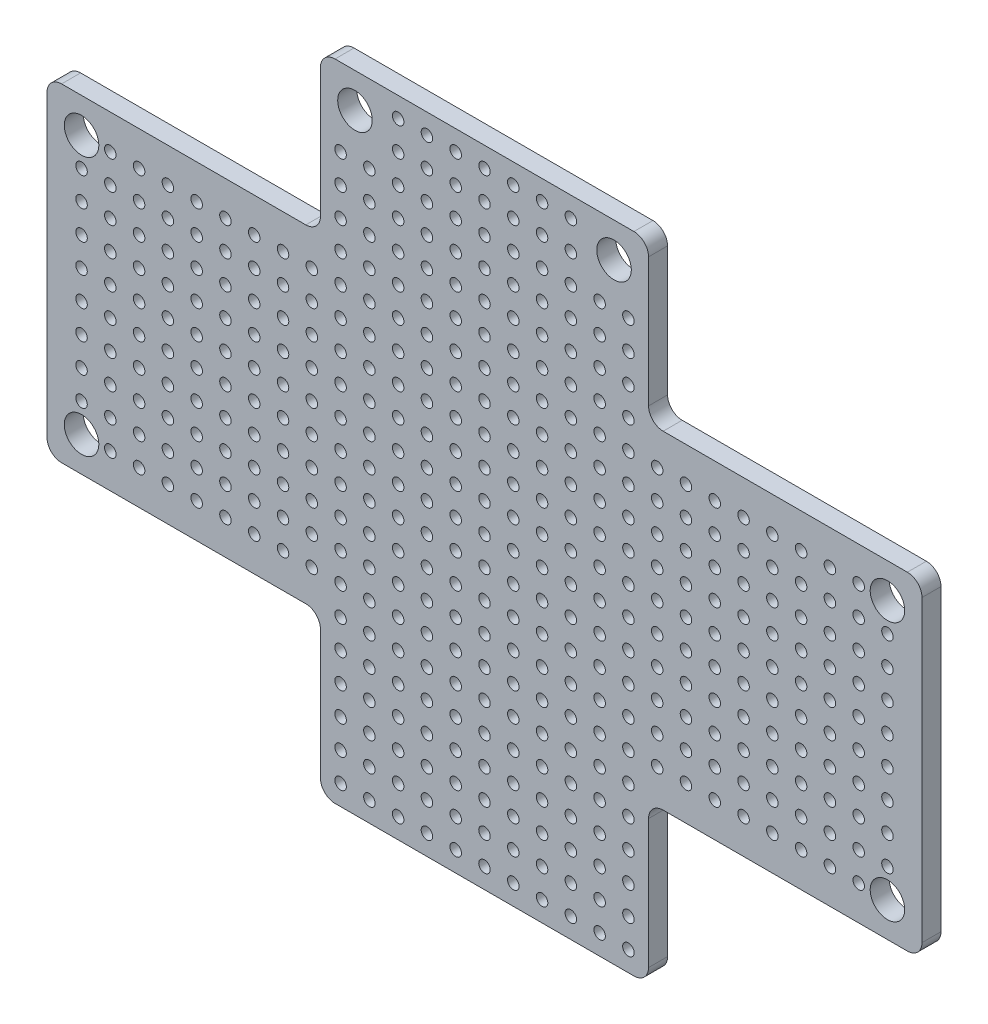
SolidWorks part; units mm, degrees
ref_plane "Front Plane" through (0, 0, 0) normal (0, 0, 1) x (1, 0, 0)
ref_plane "Top Plane" through (0, 0, 0) normal (0, 1, 0) x (1, 0, 0)
ref_plane "Right Plane" through (0, 0, 0) normal (1, 0, 0) x (0, 0, -1)
sketch "Sketch1" plane through (0, 0, 0) normal (0, 0, 1) x (1, 0, 0)
  line L0 (0, 14.25) -> (76, 14.25) construction
  line L1 (0, 0) -> (23.75, 0)
  line L2 (0, 0) -> (0, 28.5)
  line L3 (0, 28.5) -> (23.75, 28.5)
  line L4 (76, 0) -> (76, 28.5)
  line L5 (38, -42.734) -> (38, 127.234) construction
  line L6 (0, 25.5) -> (76, 25.5) construction
  line L7 (76, 3) -> (0, 3) construction
  line L8 (73, 0) -> (73, 28.5) construction
  line L9 (3, 0) -> (3, 28.5) construction
  line L12 (23.75, 28.5) -> (23.75, 42.25)
  line L13 (23.75, 42.25) -> (52.25, 42.25)
  line L14 (52.25, 42.25) -> (52.25, 28.5)
  line L15 (52.25, -13.75) -> (52.25, 0)
  line L16 (23.75, -13.75) -> (52.25, -13.75)
  line L17 (23.75, 0) -> (23.75, -13.75)
  line L18 (52.25, 28.5) -> (76, 28.5)
  line L19 (52.25, 0) -> (76, 0)
  line L20 (25.5, 25.5) -> (25.5, 28) construction
  circle A0 centre (3, 25.5) radius 1.5
  circle A1 centre (73, 25.5) radius 1.5
  circle A2 centre (3, 3) radius 1.5
  circle A3 centre (73, 3) radius 1.5
  circle A4 centre (26.75, 39.25) radius 1.5
  circle A5 centre (5.5, 3) radius 0.5
  circle A6 centre (8, 3) radius 0.5
  circle A7 centre (10.5, 3) radius 0.5
  circle A8 centre (13, 3) radius 0.5
  circle A9 centre (15.5, 3) radius 0.5
  circle A10 centre (18, 3) radius 0.5
  circle A11 centre (20.5, 3) radius 0.5
  circle A12 centre (23, 3) radius 0.5
  circle A13 centre (25.5, 3) radius 0.5
  circle A14 centre (28, 3) radius 0.5
  circle A15 centre (30.5, 3) radius 0.5
  circle A16 centre (33, 3) radius 0.5
  circle A17 centre (35.5, 3) radius 0.5
  circle A18 centre (38, 3) radius 0.5
  circle A19 centre (40.5, 3) radius 0.5
  circle A20 centre (43, 3) radius 0.5
  circle A21 centre (45.5, 3) radius 0.5
  circle A22 centre (48, 3) radius 0.5
  circle A23 centre (50.5, 3) radius 0.5
  circle A24 centre (53, 3) radius 0.5
  circle A25 centre (55.5, 3) radius 0.5
  circle A26 centre (58, 3) radius 0.5
  circle A27 centre (60.5, 3) radius 0.5
  circle A28 centre (63, 3) radius 0.5
  circle A29 centre (65.5, 3) radius 0.5
  circle A30 centre (68, 3) radius 0.5
  circle A31 centre (70.5, 3) radius 0.5
  circle A32 centre (49.25, 39.25) radius 1.5
  circle A33 centre (5.5, 5.5) radius 0.5
  circle A34 centre (8, 5.5) radius 0.5
  circle A35 centre (10.5, 5.5) radius 0.5
  circle A36 centre (13, 5.5) radius 0.5
  circle A37 centre (15.5, 5.5) radius 0.5
  circle A38 centre (18, 5.5) radius 0.5
  circle A39 centre (20.5, 5.5) radius 0.5
  circle A40 centre (23, 5.5) radius 0.5
  circle A41 centre (25.5, 5.5) radius 0.5
  circle A42 centre (28, 5.5) radius 0.5
  circle A43 centre (30.5, 5.5) radius 0.5
  circle A44 centre (33, 5.5) radius 0.5
  circle A45 centre (35.5, 5.5) radius 0.5
  circle A46 centre (38, 5.5) radius 0.5
  circle A47 centre (40.5, 5.5) radius 0.5
  circle A48 centre (43, 5.5) radius 0.5
  circle A49 centre (45.5, 5.5) radius 0.5
  circle A50 centre (48, 5.5) radius 0.5
  circle A51 centre (50.5, 5.5) radius 0.5
  circle A52 centre (53, 5.5) radius 0.5
  circle A53 centre (55.5, 5.5) radius 0.5
  circle A54 centre (58, 5.5) radius 0.5
  circle A55 centre (60.5, 5.5) radius 0.5
  circle A56 centre (63, 5.5) radius 0.5
  circle A57 centre (65.5, 5.5) radius 0.5
  circle A58 centre (68, 5.5) radius 0.5
  circle A59 centre (70.5, 5.5) radius 0.5
  circle A60 centre (73, 5.5) radius 0.5
  circle A61 centre (5.5, 8) radius 0.5
  circle A62 centre (8, 8) radius 0.5
  circle A63 centre (10.5, 8) radius 0.5
  circle A64 centre (13, 8) radius 0.5
  circle A65 centre (15.5, 8) radius 0.5
  circle A66 centre (18, 8) radius 0.5
  circle A67 centre (20.5, 8) radius 0.5
  circle A68 centre (23, 8) radius 0.5
  circle A69 centre (25.5, 8) radius 0.5
  circle A70 centre (28, 8) radius 0.5
  circle A71 centre (30.5, 8) radius 0.5
  circle A72 centre (33, 8) radius 0.5
  circle A73 centre (35.5, 8) radius 0.5
  circle A74 centre (38, 8) radius 0.5
  circle A75 centre (40.5, 8) radius 0.5
  circle A76 centre (43, 8) radius 0.5
  circle A77 centre (45.5, 8) radius 0.5
  circle A78 centre (48, 8) radius 0.5
  circle A79 centre (50.5, 8) radius 0.5
  circle A80 centre (53, 8) radius 0.5
  circle A81 centre (55.5, 8) radius 0.5
  circle A82 centre (58, 8) radius 0.5
  circle A83 centre (60.5, 8) radius 0.5
  circle A84 centre (63, 8) radius 0.5
  circle A85 centre (65.5, 8) radius 0.5
  circle A86 centre (68, 8) radius 0.5
  circle A87 centre (70.5, 8) radius 0.5
  circle A88 centre (73, 8) radius 0.5
  circle A89 centre (5.5, 10.5) radius 0.5
  circle A90 centre (8, 10.5) radius 0.5
  circle A91 centre (10.5, 10.5) radius 0.5
  circle A92 centre (13, 10.5) radius 0.5
  circle A93 centre (15.5, 10.5) radius 0.5
  circle A94 centre (18, 10.5) radius 0.5
  circle A95 centre (20.5, 10.5) radius 0.5
  circle A96 centre (23, 10.5) radius 0.5
  circle A97 centre (25.5, 10.5) radius 0.5
  circle A98 centre (28, 10.5) radius 0.5
  circle A99 centre (30.5, 10.5) radius 0.5
  circle A100 centre (33, 10.5) radius 0.5
  circle A101 centre (35.5, 10.5) radius 0.5
  circle A102 centre (38, 10.5) radius 0.5
  circle A103 centre (40.5, 10.5) radius 0.5
  circle A104 centre (43, 10.5) radius 0.5
  circle A105 centre (45.5, 10.5) radius 0.5
  circle A106 centre (48, 10.5) radius 0.5
  circle A107 centre (50.5, 10.5) radius 0.5
  circle A108 centre (53, 10.5) radius 0.5
  circle A109 centre (55.5, 10.5) radius 0.5
  circle A110 centre (58, 10.5) radius 0.5
  circle A111 centre (60.5, 10.5) radius 0.5
  circle A112 centre (63, 10.5) radius 0.5
  circle A113 centre (65.5, 10.5) radius 0.5
  circle A114 centre (68, 10.5) radius 0.5
  circle A115 centre (70.5, 10.5) radius 0.5
  circle A116 centre (73, 10.5) radius 0.5
  circle A117 centre (5.5, 13) radius 0.5
  circle A118 centre (8, 13) radius 0.5
  circle A119 centre (10.5, 13) radius 0.5
  circle A120 centre (13, 13) radius 0.5
  circle A121 centre (15.5, 13) radius 0.5
  circle A122 centre (18, 13) radius 0.5
  circle A123 centre (20.5, 13) radius 0.5
  circle A124 centre (23, 13) radius 0.5
  circle A125 centre (25.5, 13) radius 0.5
  circle A126 centre (28, 13) radius 0.5
  circle A127 centre (30.5, 13) radius 0.5
  circle A128 centre (33, 13) radius 0.5
  circle A129 centre (35.5, 13) radius 0.5
  circle A130 centre (38, 13) radius 0.5
  circle A131 centre (40.5, 13) radius 0.5
  circle A132 centre (43, 13) radius 0.5
  circle A133 centre (45.5, 13) radius 0.5
  circle A134 centre (48, 13) radius 0.5
  circle A135 centre (50.5, 13) radius 0.5
  circle A136 centre (53, 13) radius 0.5
  circle A137 centre (55.5, 13) radius 0.5
  circle A138 centre (58, 13) radius 0.5
  circle A139 centre (60.5, 13) radius 0.5
  circle A140 centre (63, 13) radius 0.5
  circle A141 centre (65.5, 13) radius 0.5
  circle A142 centre (68, 13) radius 0.5
  circle A143 centre (70.5, 13) radius 0.5
  circle A144 centre (73, 13) radius 0.5
  circle A145 centre (5.5, 15.5) radius 0.5
  circle A146 centre (8, 15.5) radius 0.5
  circle A147 centre (10.5, 15.5) radius 0.5
  circle A148 centre (13, 15.5) radius 0.5
  circle A149 centre (15.5, 15.5) radius 0.5
  circle A150 centre (18, 15.5) radius 0.5
  circle A151 centre (20.5, 15.5) radius 0.5
  circle A152 centre (23, 15.5) radius 0.5
  circle A153 centre (25.5, 15.5) radius 0.5
  circle A154 centre (28, 15.5) radius 0.5
  circle A155 centre (30.5, 15.5) radius 0.5
  circle A156 centre (33, 15.5) radius 0.5
  circle A157 centre (35.5, 15.5) radius 0.5
  circle A158 centre (38, 15.5) radius 0.5
  circle A159 centre (40.5, 15.5) radius 0.5
  circle A160 centre (43, 15.5) radius 0.5
  circle A161 centre (45.5, 15.5) radius 0.5
  circle A162 centre (48, 15.5) radius 0.5
  circle A163 centre (50.5, 15.5) radius 0.5
  circle A164 centre (53, 15.5) radius 0.5
  circle A165 centre (55.5, 15.5) radius 0.5
  circle A166 centre (58, 15.5) radius 0.5
  circle A167 centre (60.5, 15.5) radius 0.5
  circle A168 centre (63, 15.5) radius 0.5
  circle A169 centre (65.5, 15.5) radius 0.5
  circle A170 centre (68, 15.5) radius 0.5
  circle A171 centre (70.5, 15.5) radius 0.5
  circle A172 centre (73, 15.5) radius 0.5
  circle A173 centre (5.5, 18) radius 0.5
  circle A174 centre (8, 18) radius 0.5
  circle A175 centre (10.5, 18) radius 0.5
  circle A176 centre (13, 18) radius 0.5
  circle A177 centre (15.5, 18) radius 0.5
  circle A178 centre (18, 18) radius 0.5
  circle A179 centre (20.5, 18) radius 0.5
  circle A180 centre (23, 18) radius 0.5
  circle A181 centre (25.5, 18) radius 0.5
  circle A182 centre (28, 18) radius 0.5
  circle A183 centre (30.5, 18) radius 0.5
  circle A184 centre (33, 18) radius 0.5
  circle A185 centre (35.5, 18) radius 0.5
  circle A186 centre (38, 18) radius 0.5
  circle A187 centre (40.5, 18) radius 0.5
  circle A188 centre (43, 18) radius 0.5
  circle A189 centre (45.5, 18) radius 0.5
  circle A190 centre (48, 18) radius 0.5
  circle A191 centre (50.5, 18) radius 0.5
  circle A192 centre (53, 18) radius 0.5
  circle A193 centre (55.5, 18) radius 0.5
  circle A194 centre (58, 18) radius 0.5
  circle A195 centre (60.5, 18) radius 0.5
  circle A196 centre (63, 18) radius 0.5
  circle A197 centre (65.5, 18) radius 0.5
  circle A198 centre (68, 18) radius 0.5
  circle A199 centre (70.5, 18) radius 0.5
  circle A200 centre (73, 18) radius 0.5
  circle A201 centre (5.5, 20.5) radius 0.5
  circle A202 centre (8, 20.5) radius 0.5
  circle A203 centre (10.5, 20.5) radius 0.5
  circle A204 centre (13, 20.5) radius 0.5
  circle A205 centre (15.5, 20.5) radius 0.5
  circle A206 centre (18, 20.5) radius 0.5
  circle A207 centre (20.5, 20.5) radius 0.5
  circle A208 centre (23, 20.5) radius 0.5
  circle A209 centre (25.5, 20.5) radius 0.5
  circle A210 centre (28, 20.5) radius 0.5
  circle A211 centre (30.5, 20.5) radius 0.5
  circle A212 centre (33, 20.5) radius 0.5
  circle A213 centre (35.5, 20.5) radius 0.5
  circle A214 centre (38, 20.5) radius 0.5
  circle A215 centre (40.5, 20.5) radius 0.5
  circle A216 centre (43, 20.5) radius 0.5
  circle A217 centre (45.5, 20.5) radius 0.5
  circle A218 centre (48, 20.5) radius 0.5
  circle A219 centre (50.5, 20.5) radius 0.5
  circle A220 centre (53, 20.5) radius 0.5
  circle A221 centre (55.5, 20.5) radius 0.5
  circle A222 centre (58, 20.5) radius 0.5
  circle A223 centre (60.5, 20.5) radius 0.5
  circle A224 centre (63, 20.5) radius 0.5
  circle A225 centre (65.5, 20.5) radius 0.5
  circle A226 centre (68, 20.5) radius 0.5
  circle A227 centre (70.5, 20.5) radius 0.5
  circle A228 centre (73, 20.5) radius 0.5
  circle A229 centre (5.5, 23) radius 0.5
  circle A230 centre (8, 23) radius 0.5
  circle A231 centre (10.5, 23) radius 0.5
  circle A232 centre (13, 23) radius 0.5
  circle A233 centre (15.5, 23) radius 0.5
  circle A234 centre (18, 23) radius 0.5
  circle A235 centre (20.5, 23) radius 0.5
  circle A236 centre (23, 23) radius 0.5
  circle A237 centre (25.5, 23) radius 0.5
  circle A238 centre (28, 23) radius 0.5
  circle A239 centre (30.5, 23) radius 0.5
  circle A240 centre (33, 23) radius 0.5
  circle A241 centre (35.5, 23) radius 0.5
  circle A242 centre (38, 23) radius 0.5
  circle A243 centre (40.5, 23) radius 0.5
  circle A244 centre (43, 23) radius 0.5
  circle A245 centre (45.5, 23) radius 0.5
  circle A246 centre (48, 23) radius 0.5
  circle A247 centre (50.5, 23) radius 0.5
  circle A248 centre (53, 23) radius 0.5
  circle A249 centre (55.5, 23) radius 0.5
  circle A250 centre (58, 23) radius 0.5
  circle A251 centre (60.5, 23) radius 0.5
  circle A252 centre (63, 23) radius 0.5
  circle A253 centre (65.5, 23) radius 0.5
  circle A254 centre (68, 23) radius 0.5
  circle A255 centre (70.5, 23) radius 0.5
  circle A256 centre (73, 23) radius 0.5
  circle A257 centre (5.5, 25.5) radius 0.5
  circle A258 centre (8, 25.5) radius 0.5
  circle A259 centre (10.5, 25.5) radius 0.5
  circle A260 centre (13, 25.5) radius 0.5
  circle A261 centre (15.5, 25.5) radius 0.5
  circle A262 centre (18, 25.5) radius 0.5
  circle A263 centre (20.5, 25.5) radius 0.5
  circle A264 centre (23, 25.5) radius 0.5
  circle A265 centre (25.5, 25.5) radius 0.5
  circle A266 centre (28, 25.5) radius 0.5
  circle A267 centre (30.5, 25.5) radius 0.5
  circle A268 centre (33, 25.5) radius 0.5
  circle A269 centre (35.5, 25.5) radius 0.5
  circle A270 centre (38, 25.5) radius 0.5
  circle A271 centre (40.5, 25.5) radius 0.5
  circle A272 centre (43, 25.5) radius 0.5
  circle A273 centre (45.5, 25.5) radius 0.5
  circle A274 centre (48, 25.5) radius 0.5
  circle A275 centre (50.5, 25.5) radius 0.5
  circle A276 centre (53, 25.5) radius 0.5
  circle A277 centre (55.5, 25.5) radius 0.5
  circle A278 centre (58, 25.5) radius 0.5
  circle A279 centre (60.5, 25.5) radius 0.5
  circle A280 centre (63, 25.5) radius 0.5
  circle A281 centre (65.5, 25.5) radius 0.5
  circle A282 centre (68, 25.5) radius 0.5
  circle A283 centre (70.5, 25.5) radius 0.5
  circle A285 centre (3, 5.5) radius 0.5
  circle A286 centre (3, 8) radius 0.5
  circle A287 centre (3, 10.5) radius 0.5
  circle A288 centre (3, 13) radius 0.5
  circle A289 centre (3, 15.5) radius 0.5
  circle A290 centre (3, 18) radius 0.5
  circle A291 centre (3, 20.5) radius 0.5
  circle A292 centre (3, 23) radius 0.5
  circle A294 centre (25.5, 28) radius 0.5
  circle A295 centre (28, 28) radius 0.5
  circle A296 centre (30.5, 28) radius 0.5
  circle A297 centre (33, 28) radius 0.5
  circle A298 centre (35.5, 28) radius 0.5
  circle A299 centre (38, 28) radius 0.5
  circle A300 centre (40.5, 28) radius 0.5
  circle A301 centre (43, 28) radius 0.5
  circle A302 centre (45.5, 28) radius 0.5
  circle A303 centre (48, 28) radius 0.5
  circle A304 centre (50.5, 28) radius 0.5
  circle A305 centre (25.5, 30.5) radius 0.5
  circle A306 centre (28, 30.5) radius 0.5
  circle A307 centre (30.5, 30.5) radius 0.5
  circle A308 centre (33, 30.5) radius 0.5
  circle A309 centre (35.5, 30.5) radius 0.5
  circle A310 centre (38, 30.5) radius 0.5
  circle A311 centre (40.5, 30.5) radius 0.5
  circle A312 centre (43, 30.5) radius 0.5
  circle A313 centre (45.5, 30.5) radius 0.5
  circle A314 centre (48, 30.5) radius 0.5
  circle A315 centre (50.5, 30.5) radius 0.5
  circle A316 centre (25.5, 33) radius 0.5
  circle A317 centre (28, 33) radius 0.5
  circle A318 centre (30.5, 33) radius 0.5
  circle A319 centre (33, 33) radius 0.5
  circle A320 centre (35.5, 33) radius 0.5
  circle A321 centre (38, 33) radius 0.5
  circle A322 centre (40.5, 33) radius 0.5
  circle A323 centre (43, 33) radius 0.5
  circle A324 centre (45.5, 33) radius 0.5
  circle A325 centre (48, 33) radius 0.5
  circle A326 centre (50.5, 33) radius 0.5
  circle A327 centre (25.5, 35.5) radius 0.5
  circle A328 centre (28, 35.5) radius 0.5
  circle A329 centre (30.5, 35.5) radius 0.5
  circle A330 centre (33, 35.5) radius 0.5
  circle A331 centre (35.5, 35.5) radius 0.5
  circle A332 centre (38, 35.5) radius 0.5
  circle A333 centre (40.5, 35.5) radius 0.5
  circle A334 centre (43, 35.5) radius 0.5
  circle A335 centre (45.5, 35.5) radius 0.5
  circle A336 centre (48, 35.5) radius 0.5
  circle A337 centre (50.5, 35.5) radius 0.5
  circle A340 centre (30.5, 38) radius 0.5
  circle A341 centre (33, 38) radius 0.5
  circle A342 centre (35.5, 38) radius 0.5
  circle A343 centre (38, 38) radius 0.5
  circle A344 centre (40.5, 38) radius 0.5
  circle A345 centre (43, 38) radius 0.5
  circle A346 centre (45.5, 38) radius 0.5
  circle A351 centre (30.5, 40.5) radius 0.5
  circle A352 centre (33, 40.5) radius 0.5
  circle A353 centre (35.5, 40.5) radius 0.5
  circle A354 centre (38, 40.5) radius 0.5
  circle A355 centre (40.5, 40.5) radius 0.5
  circle A356 centre (43, 40.5) radius 0.5
  circle A357 centre (45.5, 40.5) radius 0.5
  circle A384 centre (25.5, -12) radius 0.5
  circle A385 centre (25.5, -9.5) radius 0.5
  circle A386 centre (25.5, -7) radius 0.5
  circle A387 centre (25.5, -4.5) radius 0.5
  circle A388 centre (25.5, -2) radius 0.5
  circle A389 centre (25.5, 0.5) radius 0.5
  circle A410 centre (50.5, -12) radius 0.5
  circle A411 centre (48, -12) radius 0.5
  circle A412 centre (45.5, -12) radius 0.5
  circle A413 centre (43, -12) radius 0.5
  circle A414 centre (40.5, -12) radius 0.5
  circle A415 centre (38, -12) radius 0.5
  circle A416 centre (35.5, -12) radius 0.5
  circle A417 centre (33, -12) radius 0.5
  circle A418 centre (30.5, -12) radius 0.5
  circle A419 centre (28, -12) radius 0.5
  circle A420 centre (50.5, -9.5) radius 0.5
  circle A421 centre (48, -9.5) radius 0.5
  circle A422 centre (45.5, -9.5) radius 0.5
  circle A423 centre (43, -9.5) radius 0.5
  circle A424 centre (40.5, -9.5) radius 0.5
  circle A425 centre (38, -9.5) radius 0.5
  circle A426 centre (35.5, -9.5) radius 0.5
  circle A427 centre (33, -9.5) radius 0.5
  circle A428 centre (30.5, -9.5) radius 0.5
  circle A429 centre (28, -9.5) radius 0.5
  circle A430 centre (50.5, -7) radius 0.5
  circle A431 centre (48, -7) radius 0.5
  circle A432 centre (45.5, -7) radius 0.5
  circle A433 centre (43, -7) radius 0.5
  circle A434 centre (40.5, -7) radius 0.5
  circle A435 centre (38, -7) radius 0.5
  circle A436 centre (35.5, -7) radius 0.5
  circle A437 centre (33, -7) radius 0.5
  circle A438 centre (30.5, -7) radius 0.5
  circle A439 centre (28, -7) radius 0.5
  circle A440 centre (50.5, -4.5) radius 0.5
  circle A441 centre (48, -4.5) radius 0.5
  circle A442 centre (45.5, -4.5) radius 0.5
  circle A443 centre (43, -4.5) radius 0.5
  circle A444 centre (40.5, -4.5) radius 0.5
  circle A445 centre (38, -4.5) radius 0.5
  circle A446 centre (35.5, -4.5) radius 0.5
  circle A447 centre (33, -4.5) radius 0.5
  circle A448 centre (30.5, -4.5) radius 0.5
  circle A449 centre (28, -4.5) radius 0.5
  circle A450 centre (50.5, -2) radius 0.5
  circle A451 centre (48, -2) radius 0.5
  circle A452 centre (45.5, -2) radius 0.5
  circle A453 centre (43, -2) radius 0.5
  circle A454 centre (40.5, -2) radius 0.5
  circle A455 centre (38, -2) radius 0.5
  circle A456 centre (35.5, -2) radius 0.5
  circle A457 centre (33, -2) radius 0.5
  circle A458 centre (30.5, -2) radius 0.5
  circle A459 centre (28, -2) radius 0.5
  circle A460 centre (50.5, 0.5) radius 0.5
  circle A461 centre (48, 0.5) radius 0.5
  circle A462 centre (45.5, 0.5) radius 0.5
  circle A463 centre (43, 0.5) radius 0.5
  circle A464 centre (40.5, 0.5) radius 0.5
  circle A465 centre (38, 0.5) radius 0.5
  circle A466 centre (35.5, 0.5) radius 0.5
  circle A467 centre (33, 0.5) radius 0.5
  circle A468 centre (30.5, 0.5) radius 0.5
  circle A469 centre (28, 0.5) radius 0.5
  circle A571 centre (3, 3) radius 1.5 [skipped]
  circle A572 centre (25.5, 40.5) radius 0.5 [skipped]
  circle A573 centre (50.5, 40.5) radius 0.5 [skipped]
  circle A574 centre (25.5, 38) radius 0.5 [skipped]
  circle A575 centre (28, 38) radius 0.5 [skipped]
  circle A576 centre (28, 40.5) radius 0.5 [skipped]
  circle A577 centre (48, 40.5) radius 0.5 [skipped]
  circle A578 centre (48, 38) radius 0.5 [skipped]
  circle A579 centre (50.5, 38) radius 0.5 [skipped]
  point P611 (38, 42.25)
  point P612 (38, 14.25)
  dimension "D3" = 3
  dimension "D8" = 3
  dimension "D9" = 11.25
  dimension "D10" = 76
  dimension "D11" = 35
  dimension "D12" = 3
  dimension "D13" = 3
  dimension "D14" = 3
  dimension "D15" = 1
  dimension "D20" = 2.5
  dimension "D1" = 28.5
  dimension "D2" = 3
  dimension "D4" = 3
  dimension "D5" = 3
  dimension "D16" = 28.5
  dimension "D17" = 13.75
  dimension "D19" = 2.5
  dimension "D6" = 2
  dimension "D7" = 2
  dimension "D18" = 7
extrude "Boss-Extrude1" add sketch "Sketch1" along normal blind 1.651
fillet "Fillet1" radius 1.27 12 edges at (0, 28.5, 0.8255) (0, 0, 0.8255) (52.25, 42.25, 0.8255) (23.75, 42.25, 0.8255) (23.75, 28.5, 0.8255) (23.75, 0, 0.8255) (23.75, -13.75, 0.8255) (52.25, -13.75, 0.8255) (52.25, 28.5, 0.8255) (52.25, 0, 0.8255) (76, 0, 0.8255) (76, 28.5, 0.8255)
ref_plane "Plane1" through (0, 14.25, 0) normal (0, -1, 0) x (1, 0, 0)
ref_plane "Plane2" through (38, 0, 0) normal (1, 0, 0) x (0, 0, -1)
